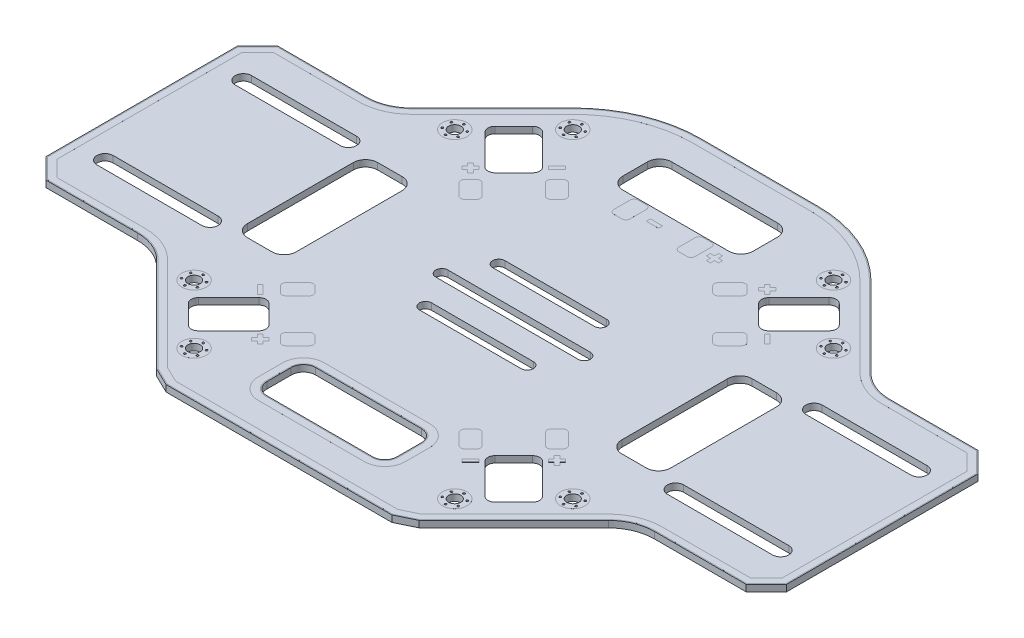
SolidWorks part; units mm, degrees
material "Baseplate Screw Material"
ref_plane "Front Plane" through (0, 0, 0) normal (0, 0, 1) x (1, 0, 0)
ref_plane "Top Plane" through (0, 0, 0) normal (0, 1, 0) x (1, 0, 0)
ref_plane "Right Plane" through (0, 0, 0) normal (1, 0, 0) x (0, 0, -1)
sketch "Sketch1" plane through (0, 0, 0) normal (0, 1, 0) x (1, 0, 0)
  line L0 (0, 60.3186) -> (0, -57.6814) construction
  line L1 (-27.75, -57.6814) -> (27.75, -57.6814)
  line L2 (-13, -47.6814) -> (13, -47.6814)
  line L3 (-16, -38.6814) -> (-16, -44.6814)
  line L4 (16, -38.6814) -> (16, -44.6814)
  line L5 (-16, -41.6814) -> (16, -41.6814) construction
  line L6 (-13, -35.6814) -> (13, -35.6814)
  line L7 (-27.75, -57.6814) -> (-32.25, -55.502)
  line L8 (27.75, -57.6814) -> (32.25, -55.502)
  line L9 (-32.25, -55.502) -> (32.25, -55.502) construction
  line L10 (32.25, -55.502) -> (55.502, -32.25)
  line L11 (-32.25, -55.502) -> (-55.502, -32.25)
  line L12 (-43.876, 43.876) -> (43.876, -43.876) construction
  line L13 (-43.876, -43.876) -> (43.876, 43.876) construction
  line L14 (37.6888, -42.285) -> (42.285, -37.6888)
  line L15 (27.7893, -34.8604) -> (35.2139, -42.285)
  line L16 (34.8604, -27.7893) -> (42.285, -35.2139)
  line L17 (31.5016, -38.5727) -> (38.5727, -31.5016) construction
  line L18 (27.7893, -32.3855) -> (32.3855, -27.7893)
  line L19 (-38.5727, -31.5016) -> (-31.5016, -38.5727) construction
  line L20 (-35.2139, -42.285) -> (-27.7893, -34.8604)
  line L21 (-42.285, -35.2139) -> (-34.8604, -27.7893)
  line L22 (-32.3855, -27.7893) -> (-27.7893, -32.3855)
  line L23 (-42.285, -37.6888) -> (-37.6888, -42.285)
  line L24 (-63.5, -28.9371) -> (63.5, -28.9371) construction
  line L25 (63.5, -28.9371) -> (86, -28.9371)
  line L26 (-63.5, -28.9371) -> (-86, -28.9371)
  line L27 (-91, -23.9371) -> (-91, 23.0629)
  line L28 (91, -23.9371) -> (91, 23.0629)
  line L29 (-86, -28.9371) -> (-86, 28.0629) construction
  line L30 (86, -28.9371) -> (86, 28.0629) construction
  line L31 (-91, -0.4371) -> (-86, -0.4371) construction
  line L32 (86, -0.4371) -> (91, -0.4371) construction
  line L33 (86, -28.9371) -> (91, -23.9371)
  line L34 (-91, -23.9371) -> (-86, -28.9371)
  line L35 (91, 23.0629) -> (86, 28.0629)
  line L36 (-91, 23.0629) -> (-86, 28.0629)
  line L37 (-56.4271, 31.3248) -> (-36.6281, 51.1238)
  line L38 (36.6281, 51.1238) -> (56.4271, 31.3248)
  line L39 (-35.2139, 42.285) -> (-27.7893, 34.8604)
  line L40 (-36.6281, 51.1238) -> (-27.7893, 42.285) construction
  line L41 (-27.7893, 42.285) -> (-31.5016, 38.5727) construction
  line L42 (-42.285, 35.2139) -> (-34.8604, 27.7893)
  line L43 (-31.5016, 38.5727) -> (-38.5727, 31.5016) construction
  line L44 (-42.285, 37.6888) -> (-37.6888, 42.285)
  line L45 (-32.3855, 27.7893) -> (-27.7893, 32.3855)
  line L46 (-86, 28.0629) -> (-64.3021, 28.0629)
  line L47 (86, 28.0629) -> (64.3021, 28.0629)
  line L48 (37.6888, 42.285) -> (42.285, 37.6888)
  line L49 (27.7893, 32.3855) -> (32.3855, 27.7893)
  line L50 (27.7893, 34.8604) -> (35.2139, 42.285)
  line L51 (34.8604, 27.7893) -> (42.285, 35.2139)
  line L52 (31.5016, 38.5727) -> (38.5727, 31.5016) construction
  line L53 (31.5016, 38.5727) -> (27.7893, 42.285) construction
  line L54 (27.7893, 42.285) -> (36.6281, 51.1238) construction
  line L55 (-14.43, 60.3186) -> (14.43, 60.3186)
  line L56 (-13, 51.8186) -> (13, 51.8186)
  line L57 (-13, 39.8186) -> (13, 39.8186)
  line L58 (16, 48.8186) -> (16, 42.8186)
  line L59 (-16, 48.8186) -> (-16, 42.8186)
  line L60 (-12.5, -10.6814) -> (12.5, -10.6814)
  line L61 (-12.5, -7.6814) -> (12.5, -7.6814)
  line L62 (-17.5, -1.6814) -> (17.5, -1.6814)
  line L63 (-17.5, 1.3186) -> (17.5, 1.3186)
  line L64 (-12.5, 7.3186) -> (12.5, 7.3186)
  line L65 (-12.5, 10.3186) -> (12.5, 10.3186)
  line L66 (-52, 12.5629) -> (-52, -13.4371)
  line L67 (-86, -0.4371) -> (-52, -0.4371) construction
  line L68 (-40, 12.5629) -> (-40, -13.4371)
  line L69 (52, 12.5629) -> (52, -13.4371)
  line L70 (-49, 15.5629) -> (-43, 15.5629)
  line L71 (-49, -16.4371) -> (-43, -16.4371)
  line L72 (86, -0.4371) -> (52, -0.4371) construction
  line L73 (40, 12.5629) -> (40, -13.4371)
  line L74 (43, 15.5629) -> (49, 15.5629)
  line L75 (43, -16.4371) -> (49, -16.4371)
  line L76 (-83, 18.5629) -> (-57.2, 18.5629)
  line L77 (-83, 14.5629) -> (-57.2, 14.5629)
  line L78 (-83, -15.4371) -> (-57.2, -15.4371)
  line L79 (-83, -19.4371) -> (-57.2, -19.4371)
  line L80 (57.2, -15.4371) -> (83, -15.4371)
  line L81 (57.2, -19.4371) -> (83, -19.4371)
  line L82 (57.2, 18.5629) -> (83, 18.5629)
  line L83 (57.2, 14.5629) -> (83, 14.5629)
  line L84 (-46.5276, 32.0319) -> (-32.0319, 46.5276) construction
  line L85 (32.0319, -46.5276) -> (46.5276, -32.0319) construction
  arc A0 (-16, -44.6814) -> (-13, -47.6814) centre (-13, -44.6814) ccw
  arc A1 (-13, -35.6814) -> (-16, -38.6814) centre (-13, -38.6814) ccw
  arc A2 (16, -38.6814) -> (13, -35.6814) centre (13, -38.6814) ccw
  arc A3 (13, -47.6814) -> (16, -44.6814) centre (13, -44.6814) ccw
  arc A4 (27.7893, -32.3855) -> (27.7893, -34.8604) centre (29.0267, -33.6229) ccw
  arc A5 (34.8604, -27.7893) -> (32.3855, -27.7893) centre (33.6229, -29.0267) ccw
  arc A6 (35.2139, -42.285) -> (37.6888, -42.285) centre (36.4514, -41.0475) ccw
  arc A7 (42.285, -37.6888) -> (42.285, -35.2139) centre (41.0475, -36.4514) ccw
  arc A8 (-37.6888, -42.285) -> (-35.2139, -42.285) centre (-36.4514, -41.0475) ccw
  arc A9 (-42.285, -35.2139) -> (-42.285, -37.6888) centre (-41.0475, -36.4514) ccw
  arc A10 (-32.3855, -27.7893) -> (-34.8604, -27.7893) centre (-33.6229, -29.0267) ccw
  arc A11 (-27.7893, -34.8604) -> (-27.7893, -32.3855) centre (-29.0267, -33.6229) ccw
  arc A12 (-55.502, -32.25) -> (-63.5, -28.9371) centre (-63.5, -40.248) ccw
  arc A13 (63.5, -28.9371) -> (55.502, -32.25) centre (63.5, -40.248) ccw
  arc A14 (-42.285, 37.6888) -> (-42.285, 35.2139) centre (-41.0475, 36.4514) ccw
  arc A15 (-35.2139, 42.285) -> (-37.6888, 42.285) centre (-36.4514, 41.0475) ccw
  arc A16 (-27.7893, 32.3855) -> (-27.7893, 34.8604) centre (-29.0267, 33.6229) ccw
  arc A17 (-34.8604, 27.7893) -> (-32.3855, 27.7893) centre (-33.6229, 29.0267) ccw
  arc A18 (-64.3021, 28.0629) -> (-56.4271, 31.3248) centre (-64.3021, 39.1998) ccw
  arc A19 (56.4271, 31.3248) -> (64.3021, 28.0629) centre (64.3021, 39.1998) ccw
  arc A20 (27.7893, 34.8604) -> (27.7893, 32.3855) centre (29.0267, 33.6229) ccw
  arc A21 (37.6888, 42.285) -> (35.2139, 42.285) centre (36.4514, 41.0475) ccw
  arc A22 (42.285, 35.2139) -> (42.285, 37.6888) centre (41.0475, 36.4514) ccw
  arc A23 (32.3855, 27.7893) -> (34.8604, 27.7893) centre (33.6229, 29.0267) ccw
  arc A24 (-14.43, 60.3186) -> (-36.6281, 51.1238) centre (-14.43, 28.9257) ccw
  arc A25 (13, 39.8186) -> (16, 42.8186) centre (13, 42.8186) ccw
  arc A26 (36.6281, 51.1238) -> (14.43, 60.3186) centre (14.43, 28.9257) ccw
  arc A27 (16, 48.8186) -> (13, 51.8186) centre (13, 48.8186) ccw
  arc A28 (-16, 42.8186) -> (-13, 39.8186) centre (-13, 42.8186) ccw
  arc A29 (-13, 51.8186) -> (-16, 48.8186) centre (-13, 48.8186) ccw
  arc A30 (-12.5, -7.6814) -> (-12.5, -10.6814) centre (-12.5, -9.1814) ccw
  arc A31 (12.5, -10.6814) -> (12.5, -7.6814) centre (12.5, -9.1814) ccw
  arc A32 (-17.5, 1.3186) -> (-17.5, -1.6814) centre (-17.5, -0.1814) ccw
  arc A33 (17.5, -1.6814) -> (17.5, 1.3186) centre (17.5, -0.1814) ccw
  arc A34 (-12.5, 10.3186) -> (-12.5, 7.3186) centre (-12.5, 8.8186) ccw
  arc A35 (12.5, 7.3186) -> (12.5, 10.3186) centre (12.5, 8.8186) ccw
  arc A36 (-49, 15.5629) -> (-52, 12.5629) centre (-49, 12.5629) ccw
  arc A37 (-40, 12.5629) -> (-43, 15.5629) centre (-43, 12.5629) ccw
  arc A38 (-52, -13.4371) -> (-49, -16.4371) centre (-49, -13.4371) ccw
  arc A39 (-43, -16.4371) -> (-40, -13.4371) centre (-43, -13.4371) ccw
  arc A40 (43, 15.5629) -> (40, 12.5629) centre (43, 12.5629) ccw
  arc A41 (52, 12.5629) -> (49, 15.5629) centre (49, 12.5629) ccw
  arc A42 (40, -13.4371) -> (43, -16.4371) centre (43, -13.4371) ccw
  arc A43 (49, -16.4371) -> (52, -13.4371) centre (49, -13.4371) ccw
  arc A44 (-57.2, 14.5629) -> (-57.2, 18.5629) centre (-57.2, 16.5629) ccw
  arc A45 (-83, 18.5629) -> (-83, 14.5629) centre (-83, 16.5629) ccw
  arc A46 (-83, -15.4371) -> (-83, -19.4371) centre (-83, -17.4371) ccw
  arc A47 (-57.2, -19.4371) -> (-57.2, -15.4371) centre (-57.2, -17.4371) ccw
  arc A48 (57.2, -15.4371) -> (57.2, -19.4371) centre (57.2, -17.4371) ccw
  arc A49 (83, -19.4371) -> (83, -15.4371) centre (83, -17.4371) ccw
  arc A50 (57.2, 18.5629) -> (57.2, 14.5629) centre (57.2, 16.5629) ccw
  arc A51 (83, 14.5629) -> (83, 18.5629) centre (83, 16.5629) ccw
  circle A52 centre (-32.0319, 46.5276) radius 1.5
  circle A53 centre (-46.5276, 32.0319) radius 1.5
  circle A54 centre (32.0319, -46.5276) radius 1.5
  circle A55 centre (46.5276, -32.0319) radius 1.5
  circle A56 centre (-46.5276, -32.0319) radius 1.5
  circle A57 centre (-32.0319, -46.5276) radius 1.5
  circle A58 centre (32.0319, 46.5276) radius 1.5
  circle A59 centre (46.5276, 32.0319) radius 1.5
  point P4 (-35.0371, 35.0371)
  point P5 (0, -47.6814)
  point P14 (0, -41.6814)
  point P15 (0, -35.6814)
  point P19 (0, -55.502)
  point P29 (0, 0)
  point P30 (39.9869, -39.9869)
  point P32 (0, 0)
  point P42 (30.0874, -30.0874)
  point P43 (35.0371, -35.0371)
  point P50 (-35.0371, -35.0371)
  point P53 (-38.5727, -31.5016)
  point P62 (-39.9869, -39.9869)
  point P63 (-30.0874, -30.0874)
  point P70 (0, -28.9371)
  point P99 (-39.9869, 39.9869)
  point P102 (-30.0874, 30.0874)
  point P119 (35.0371, 35.0371)
  point P122 (39.9869, 39.9869)
  point P123 (30.0874, 30.0874)
  point P135 (0, 51.8186)
  point P138 (0, 39.8186)
  point P147 (0, -10.6814)
  point P151 (-14, -9.1814)
  point P153 (14, -9.1814)
  point P156 (0, -1.6814)
  point P158 (-19, -0.1814)
  point P162 (19, -0.1814)
  point P167 (0, 7.3186)
  point P203 (-85, 16.5629)
  point P205 (-55.2, 16.5629)
  point P217 (85, -17.4371)
  point P229 (-39.2798, 39.2798)
  point P232 (39.2798, -39.2798)
  dimension "D5" = 12
  dimension "D6" = 55.5
  dimension "D14" = 14
  dimension "D15" = 127
  dimension "D16" = 22.5
  dimension "D23" = 8.5
  dimension "D24" = 25
  dimension "D25" = 3
  dimension "D28" = 3
  dimension "D31" = 39
  dimension "D32" = 9.5
  dimension "D34" = 29.8
  dimension "D38" = 6
  dimension "D39" = 3
  dimension "D1" = 118
  dimension "D2" = 10
  dimension "D3" = 32
  dimension "D4" = 6
  dimension "D7" = 64.5
  dimension "D8" = 5
  dimension "D9" = 124.1
  dimension "D10" = 45
  dimension "D11" = 5.5
  dimension "D12" = 6.5
  dimension "D13" = 10
  dimension "D17" = 22.5
  dimension "D18" = 5
  dimension "D19" = 45
  dimension "D20" = 47
  dimension "D21" = 28
  dimension "D22" = 5.25
  dimension "D26" = 28
  dimension "D27" = 6
  dimension "D29" = 38
  dimension "D30" = 6
  dimension "D33" = 4
  dimension "D35" = 6
  dimension "D36" = 9.5
  dimension "D37" = 4
  dimension "D40" = 6.5
  dimension "D41" = 6.5
extrude "Boss-Extrude1" add sketch "Sketch1" along normal blind 0.8 and the other way blind 0.8
sketch "Sketch2" plane through (0, 0.8, 0) normal (0, 1, 0) x (1, 0, 0)
  line L0 (-27.6926, -57.4314) -> (27.6926, -57.4314)
  line L1 (-27.75, -57.6814) -> (27.75, -57.6814) construction
  line L2 (-27.6926, -57.4314) -> (-32.1031, -55.2953)
  line L3 (-32.25, -55.502) -> (-27.75, -57.6814) construction
  line L4 (27.6926, -57.4314) -> (32.1031, -55.2953)
  line L5 (27.75, -57.6814) -> (32.25, -55.502) construction
  line L6 (0, -57.6814) -> (0, -57.4314) construction
  line L7 (-32.1031, -55.2953) -> (-55.3252, -32.0732)
  line L8 (-55.502, -32.25) -> (-32.25, -55.502) construction
  line L9 (32.1031, -55.2953) -> (55.3252, -32.0732)
  line L10 (32.25, -55.502) -> (55.502, -32.25) construction
  line L11 (-85.8964, -28.6871) -> (-63.5, -28.6871)
  line L12 (-85.8964, -28.6871) -> (-90.75, -23.8335)
  line L13 (-91, -23.9371) -> (-86, -28.9371) construction
  line L14 (-86, -28.9371) -> (-63.5, -28.9371) construction
  line L15 (63.5, -28.6871) -> (85.8964, -28.6871)
  line L16 (85.8964, -28.6871) -> (90.75, -23.8335)
  line L17 (-90.75, -23.8335) -> (-90.75, 22.9593)
  line L18 (-91, 23.0629) -> (-91, -23.9371) construction
  line L19 (-90.75, 22.9593) -> (-85.8964, 27.8129)
  line L20 (-85.8964, 27.8129) -> (-64.3021, 27.8129)
  line L21 (-64.3021, 28.0629) -> (-86, 28.0629) construction
  line L22 (-56.2503, 31.1481) -> (-36.4514, 50.947)
  line L23 (-36.6281, 51.1238) -> (-56.4271, 31.3248) construction
  line L24 (-14.43, 60.0686) -> (14.43, 60.0686)
  line L25 (14.43, 60.3186) -> (-14.43, 60.3186) construction
  line L26 (56.2503, 31.1481) -> (36.4514, 50.947)
  line L27 (56.4271, 31.3248) -> (36.6281, 51.1238) construction
  line L28 (64.3021, 27.8129) -> (85.8964, 27.8129)
  line L29 (86, 28.0629) -> (64.3021, 28.0629) construction
  line L30 (85.8964, 27.8129) -> (90.75, 22.9593)
  line L31 (91, 23.0629) -> (86, 28.0629) construction
  line L32 (90.75, 22.9593) -> (90.75, -23.8335)
  line L33 (-55.0836, 29.9813) -> (-35.2846, 49.7803)
  line L34 (-14.43, 58.4186) -> (14.43, 58.4186)
  line L35 (55.0836, 29.9813) -> (35.2846, 49.7803)
  line L36 (64.3021, 26.1629) -> (85.213, 26.1629)
  line L37 (85.213, 26.1629) -> (89.1, 22.2759)
  line L38 (89.1, 22.2759) -> (89.1, -23.1501)
  line L39 (85.213, -27.0371) -> (89.1, -23.1501)
  line L40 (63.5, -27.0371) -> (85.213, -27.0371)
  line L41 (31.1332, -53.9317) -> (54.1584, -30.9065)
  line L42 (27.3141, -55.7814) -> (31.1332, -53.9317)
  line L43 (-27.3141, -55.7814) -> (27.3141, -55.7814)
  line L44 (-27.3141, -55.7814) -> (-31.1332, -53.9317)
  line L45 (-31.1332, -53.9317) -> (-54.1584, -30.9065)
  line L46 (-85.213, -27.0371) -> (-63.5, -27.0371)
  line L47 (-85.213, -27.0371) -> (-89.1, -23.1501)
  line L48 (-89.1, -23.1501) -> (-89.1, 22.2759)
  line L49 (-89.1, 22.2759) -> (-85.213, 26.1629)
  line L50 (-85.213, 26.1629) -> (-64.3021, 26.1629)
  line L51 (-13, -35.4314) -> (13, -35.4314)
  line L52 (-16.25, -38.6814) -> (-16.25, -44.6814)
  line L53 (-13, -47.9314) -> (13, -47.9314)
  line L54 (16.25, -44.6814) -> (16.25, -38.6814)
  line L55 (16, -44.6814) -> (16, -38.6814) construction
  line L56 (13, -35.6814) -> (-13, -35.6814) construction
  line L57 (-16, -38.6814) -> (-16, -44.6814) construction
  line L58 (-13, -47.6814) -> (13, -47.6814) construction
  line L59 (-13, -33.6314) -> (13, -33.6314)
  line L60 (18.05, -44.6814) -> (18.05, -38.6814)
  line L61 (-13, -49.7314) -> (13, -49.7314)
  line L62 (-18.05, -38.6814) -> (-18.05, -44.6814)
  line L63 (32.0319, -43.5276) -> (32.0319, -44.2776) construction
  line L64 (-32.0319, -44.2776) -> (-33.9805, -45.4026) construction
  line L65 (-33.9805, -45.4026) -> (-33.9805, -47.6526) construction
  line L66 (-33.9805, -47.6526) -> (-32.0319, -48.7776) construction
  line L67 (-32.0319, -48.7776) -> (-30.0834, -47.6526) construction
  line L68 (-30.0834, -47.6526) -> (-30.0834, -45.4026) construction
  line L69 (-30.0834, -45.4026) -> (-32.0319, -44.2776) construction
  line L70 (-46.5276, -29.7819) -> (-48.4762, -30.9069) construction
  line L71 (-48.4762, -30.9069) -> (-48.4762, -33.1569) construction
  line L72 (-48.4762, -33.1569) -> (-46.5276, -34.2819) construction
  line L73 (-46.5276, -34.2819) -> (-44.5791, -33.1569) construction
  line L74 (-44.5791, -33.1569) -> (-44.5791, -30.9069) construction
  line L75 (-44.5791, -30.9069) -> (-46.5276, -29.7819) construction
  line L76 (-46.5276, 34.2819) -> (-48.4762, 33.1569) construction
  line L77 (-48.4762, 33.1569) -> (-48.4762, 30.9069) construction
  line L78 (-48.4762, 30.9069) -> (-46.5276, 29.7819) construction
  line L79 (-46.5276, 29.7819) -> (-44.5791, 30.9069) construction
  line L80 (-44.5791, 30.9069) -> (-44.5791, 33.1569) construction
  line L81 (-44.5791, 33.1569) -> (-46.5276, 34.2819) construction
  line L82 (-32.0319, 48.7776) -> (-33.9805, 47.6526) construction
  line L83 (-33.9805, 47.6526) -> (-33.9805, 45.4026) construction
  line L84 (-33.9805, 45.4026) -> (-32.0319, 44.2776) construction
  line L85 (-32.0319, 44.2776) -> (-30.0834, 45.4026) construction
  line L86 (-30.0834, 45.4026) -> (-30.0834, 47.6526) construction
  line L87 (-30.0834, 47.6526) -> (-32.0319, 48.7776) construction
  line L88 (32.0319, 48.7776) -> (30.0834, 47.6526) construction
  line L89 (30.0834, 47.6526) -> (30.0834, 45.4026) construction
  line L90 (30.0834, 45.4026) -> (32.0319, 44.2776) construction
  line L91 (32.0319, 44.2776) -> (33.9805, 45.4026) construction
  line L92 (33.9805, 45.4026) -> (33.9805, 47.6526) construction
  line L93 (33.9805, 47.6526) -> (32.0319, 48.7776) construction
  line L94 (46.5276, 34.2819) -> (44.5791, 33.1569) construction
  line L95 (44.5791, 33.1569) -> (44.5791, 30.9069) construction
  line L96 (44.5791, 30.9069) -> (46.5276, 29.7819) construction
  line L97 (46.5276, 29.7819) -> (48.4762, 30.9069) construction
  line L98 (48.4762, 30.9069) -> (48.4762, 33.1569) construction
  line L99 (48.4762, 33.1569) -> (46.5276, 34.2819) construction
  line L100 (46.5276, -29.7819) -> (44.5791, -30.9069) construction
  line L101 (44.5791, -30.9069) -> (44.5791, -33.1569) construction
  line L102 (44.5791, -33.1569) -> (46.5276, -34.2819) construction
  line L103 (46.5276, -34.2819) -> (48.4762, -33.1569) construction
  line L104 (48.4762, -33.1569) -> (48.4762, -30.9069) construction
  line L105 (48.4762, -30.9069) -> (46.5276, -29.7819) construction
  line L106 (32.0319, -44.2776) -> (30.0834, -45.4026) construction
  line L107 (30.0834, -45.4026) -> (30.0834, -47.6526) construction
  line L108 (30.0834, -47.6526) -> (32.0319, -48.7776) construction
  line L109 (32.0319, -48.7776) -> (33.9805, -47.6526) construction
  line L110 (33.9805, -47.6526) -> (33.9805, -45.4026) construction
  line L111 (33.9805, -45.4026) -> (32.0319, -44.2776) construction
  line L112 (32.0319, -44.2776) -> (32.0319, -45.0276) construction
  arc A0 (-55.3252, -32.0732) -> (-63.5, -28.6871) centre (-63.5, -40.248) ccw
  arc A1 (-55.502, -32.25) -> (-63.5, -28.9371) centre (-63.5, -40.248) ccw construction
  arc A2 (63.5, -28.6871) -> (55.3252, -32.0732) centre (63.5, -40.248) ccw
  arc A3 (63.5, -28.9371) -> (55.502, -32.25) centre (63.5, -40.248) ccw construction
  arc A4 (-64.3021, 27.8129) -> (-56.2503, 31.1481) centre (-64.3021, 39.1998) ccw
  arc A5 (-64.3021, 28.0629) -> (-56.4271, 31.3248) centre (-64.3021, 39.1998) ccw construction
  arc A6 (-14.43, 60.0686) -> (-36.4514, 50.947) centre (-14.43, 28.9257) ccw
  arc A7 (-14.43, 60.3186) -> (-36.6281, 51.1238) centre (-14.43, 28.9257) ccw construction
  arc A8 (36.4514, 50.947) -> (14.43, 60.0686) centre (14.43, 28.9257) ccw
  arc A9 (36.6281, 51.1238) -> (14.43, 60.3186) centre (14.43, 28.9257) ccw construction
  arc A10 (56.2503, 31.1481) -> (64.3021, 27.8129) centre (64.3021, 39.1998) ccw
  arc A11 (56.4271, 31.3248) -> (64.3021, 28.0629) centre (64.3021, 39.1998) ccw construction
  arc A12 (-14.43, 58.4186) -> (-35.2846, 49.7803) centre (-14.43, 28.9257) ccw
  arc A13 (35.2846, 49.7803) -> (14.43, 58.4186) centre (14.43, 28.9257) ccw
  arc A14 (55.0836, 29.9813) -> (64.3021, 26.1629) centre (64.3021, 39.1998) ccw
  arc A15 (63.5, -27.0371) -> (54.1584, -30.9065) centre (63.5, -40.248) ccw
  arc A16 (-54.1584, -30.9065) -> (-63.5, -27.0371) centre (-63.5, -40.248) ccw
  arc A17 (-64.3021, 26.1629) -> (-55.0836, 29.9813) centre (-64.3021, 39.1998) ccw
  arc A18 (-13, -35.4314) -> (-16.25, -38.6814) centre (-13, -38.6814) ccw
  arc A19 (16.25, -38.6814) -> (13, -35.4314) centre (13, -38.6814) ccw
  arc A20 (-16.25, -44.6814) -> (-13, -47.9314) centre (-13, -44.6814) ccw
  arc A21 (13, -47.9314) -> (16.25, -44.6814) centre (13, -44.6814) ccw
  arc A22 (-13, -35.6814) -> (-16, -38.6814) centre (-13, -38.6814) ccw construction
  arc A23 (-16, -44.6814) -> (-13, -47.6814) centre (-13, -44.6814) ccw construction
  arc A24 (16, -38.6814) -> (13, -35.6814) centre (13, -38.6814) ccw construction
  arc A25 (13, -47.6814) -> (16, -44.6814) centre (13, -44.6814) ccw construction
  arc A26 (18.05, -38.6814) -> (13, -33.6314) centre (13, -38.6814) ccw
  arc A27 (13, -49.7314) -> (18.05, -44.6814) centre (13, -44.6814) ccw
  arc A28 (-18.05, -44.6814) -> (-13, -49.7314) centre (-13, -44.6814) ccw
  arc A29 (-13, -33.6314) -> (-18.05, -38.6814) centre (-13, -38.6814) ccw
  circle A30 centre (-32.0319, -46.5276) radius 1.5
  circle A31 centre (-46.5276, -32.0319) radius 1.5
  circle A32 centre (-46.5276, 32.0319) radius 1.5
  circle A33 centre (-32.0319, 46.5276) radius 1.5
  circle A34 centre (32.0319, 46.5276) radius 1.5
  circle A35 centre (46.5276, 32.0319) radius 1.5
  circle A36 centre (46.5276, -32.0319) radius 1.5
  circle A37 centre (32.0319, -46.5276) radius 1.5
  circle A38 centre (-32.0319, -46.5276) radius 1.5 construction
  circle A39 centre (-46.5276, -32.0319) radius 1.5 construction
  circle A40 centre (-46.5276, 32.0319) radius 1.5 construction
  circle A41 centre (-32.0319, 46.5276) radius 1.5 construction
  circle A42 centre (32.0319, 46.5276) radius 1.5 construction
  circle A43 centre (46.5276, 32.0319) radius 1.5 construction
  circle A44 centre (46.5276, -32.0319) radius 1.5 construction
  circle A45 centre (32.0319, -46.5276) radius 1.5 construction
  circle A46 centre (-32.0319, -46.5276) radius 3
  circle A47 centre (-46.5276, -32.0319) radius 3
  circle A48 centre (-46.5276, 32.0319) radius 3
  circle A49 centre (-32.0319, 46.5276) radius 3
  circle A50 centre (32.0319, 46.5276) radius 3
  circle A51 centre (46.5276, 32.0319) radius 3
  circle A52 centre (46.5276, -32.0319) radius 3
  circle A53 centre (32.0319, -46.5276) radius 3
  circle A54 centre (-32.0319, -46.5276) radius 1.9486 construction
  circle A55 centre (-46.5276, -32.0319) radius 1.9486 construction
  circle A56 centre (-46.5276, 32.0319) radius 1.9486 construction
  circle A57 centre (-32.0319, 46.5276) radius 1.9486 construction
  circle A58 centre (32.0319, 46.5276) radius 1.9486 construction
  circle A59 centre (46.5276, 32.0319) radius 1.9486 construction
  circle A60 centre (46.5276, -32.0319) radius 1.9486 construction
  circle A61 centre (32.0319, -46.5276) radius 1.9486 construction
  circle A62 centre (32.0319, -44.2776) radius 0.25
  circle A63 centre (33.9805, -45.4026) radius 0.25
  circle A64 centre (33.9805, -47.6526) radius 0.25
  circle A65 centre (32.0319, -48.7776) radius 0.25
  circle A66 centre (30.0834, -47.6526) radius 0.25
  circle A67 centre (30.0834, -45.4026) radius 0.25
  circle A68 centre (46.5276, -34.2819) radius 0.25
  circle A69 centre (48.4762, -33.1569) radius 0.25
  circle A70 centre (48.4762, -30.9069) radius 0.25
  circle A71 centre (46.5276, -29.7819) radius 0.25
  circle A72 centre (44.5791, -30.9069) radius 0.25
  circle A73 centre (44.5791, -33.1569) radius 0.25
  circle A74 centre (46.5276, 29.7819) radius 0.25
  circle A75 centre (48.4762, 30.9069) radius 0.25
  circle A76 centre (48.4762, 33.1569) radius 0.25
  circle A77 centre (46.5276, 34.2819) radius 0.25
  circle A78 centre (44.5791, 33.1569) radius 0.25
  circle A79 centre (44.5791, 30.9069) radius 0.25
  circle A80 centre (32.0319, 44.2776) radius 0.25
  circle A81 centre (33.9805, 45.4026) radius 0.25
  circle A82 centre (33.9805, 47.6526) radius 0.25
  circle A83 centre (32.0319, 48.7776) radius 0.25
  circle A84 centre (30.0834, 47.6526) radius 0.25
  circle A85 centre (30.0834, 45.4026) radius 0.25
  circle A86 centre (-32.0319, 48.7776) radius 0.25
  circle A87 centre (-30.0834, 47.6526) radius 0.25
  circle A88 centre (-30.0834, 45.4026) radius 0.25
  circle A89 centre (-32.0319, 44.2776) radius 0.25
  circle A90 centre (-33.9805, 47.6526) radius 0.25
  circle A91 centre (-33.9805, 45.4026) radius 0.25
  circle A92 centre (-46.5276, 29.7819) radius 0.25
  circle A93 centre (-44.5791, 30.9069) radius 0.25
  circle A94 centre (-44.5791, 33.1569) radius 0.25
  circle A95 centre (-46.5276, 34.2819) radius 0.25
  circle A96 centre (-48.4762, 33.1569) radius 0.25
  circle A97 centre (-48.4762, 30.9069) radius 0.25
  circle A98 centre (-46.5276, -29.7819) radius 0.25
  circle A99 centre (-44.5791, -30.9069) radius 0.25
  circle A100 centre (-44.5791, -33.1569) radius 0.25
  circle A101 centre (-46.5276, -34.2819) radius 0.25
  circle A102 centre (-48.4762, -33.1569) radius 0.25
  circle A103 centre (-48.4762, -30.9069) radius 0.25
  circle A104 centre (-32.0319, -44.2776) radius 0.25
  circle A105 centre (-30.0834, -45.4026) radius 0.25
  circle A106 centre (-30.0834, -47.6526) radius 0.25
  circle A107 centre (-32.0319, -48.7776) radius 0.25
  circle A108 centre (-33.9805, -47.6526) radius 0.25
  circle A109 centre (-33.9805, -45.4026) radius 0.25
  dimension "D2" = 0.25
  dimension "D5" = 0.25
  dimension "D7" = 1.65
  dimension "D8" = 0.25
  dimension "D10" = 6
  dimension "D11" = 0.5
  dimension "D1" = 0.25
  dimension "D3" = 0.25
  dimension "D4" = 0.25
  dimension "D6" = 0.25
  dimension "D9" = 1.8
extrude "Boss-Extrude2" add sketch "Sketch2" along normal blind 0.001 contours A10 L26 A8 L24 A6 L22 A4 L20 L19 L17 L12 L11 A0 L7 L2 L0 L4 L9 A2 L15 L16 L32 L30 L28 L50 A17 L33 A12 L34 A13 L35 A14 L36 L37 L38 L39 L40 A15 L41 L42 L43 L44 L45 A16 L46 L47 L48 L49 | A46 A109 A108 A107 A106 A105 A104 A30 | A47 A103 A102 A101 A100 A99 A98 A31 | A48 A97 A96 A95 A94 A93 A92 A32 | A49 A91 A90 A89 A88 A87 A86 A33 | A50 A85 A84 A83 A82 A81 A80 A34 | A51 A79 A78 A77 A76 A75 A74 A35 | A52 A73 A72 A71 A70 A69 A68 A36 | A53 A67 A66 A65 A64 A63 A62 A37 | L59 A29 L62 A28 L61 A27 L60 A26 A21 L53 A20 L52 A18 L51 A19 L54 region at (-29.8036, 0.8, 56.1688) region at (0, 0.8, 34.0267) region at (-34.9471, 0.8, 46.5276) region at (-49.4428, 0.8, 32.0319) region at (-49.4428, 0.8, -32.0319) region at (-34.9471, 0.8, -46.5276) region at (29.1168, 0.8, -46.5276) region at (43.6125, 0.8, -32.0319) region at (43.6125, 0.8, 32.0319) region at (29.1168, 0.8, 46.5276)
mirror "Mirror1" about plane through (0, 0, 0) normal (0, 1, 0) of "Boss-Extrude2"
sketch "Sketch3" plane through (0, -0.8, 0) normal (0, -1, 0) x (1, 0, 0)
  line L0 (0, 49.7314) -> (0, 51.7314) construction
  line L1 (-13, 49.7314) -> (13, 49.7314) construction
  line L2 (-27.3141, 55.7814) -> (27.3141, 55.7814) construction
  line L3 (11, 51.7314) -> (-11, 51.7314) construction
  line L4 (11, 53.7814) -> (-11, 53.7814) construction
  line L5 (0, 53.7814) -> (0, 55.7814) construction
  line L6 (11, 51.7314) -> (11, 53.7814) construction
  line L7 (-11, 51.7314) -> (-11, 53.7814) construction
  line L8 (11.29, 53.7814) -> (-10.71, 53.7814) construction
  text T0 "<b>DJI INNOVATIONS</b>" font "MS Reference Sans Serif" height 2.05
  point P8 (0, 51.7314)
  point P11 (0, 53.7814)
  dimension "D1" = 2
  dimension "D2" = 22
  dimension "D3" = 0.29
extrude "Boss-Extrude3" add sketch "Sketch3" along normal blind 0.001
sketch "Sketch4" plane through (0, -0.8, 0) normal (0, -1, 0) x (1, 0, 0)
  line L0 (9.1282, 51.7314) -> (9.1282, 51.9909)
  line L1 (9.1282, 51.9909) -> (8.7389, 51.9909)
  line L2 (8.7389, 51.9909) -> (8.7389, 51.7314)
  line L3 (9.1282, 51.7314) -> (8.4275, 51.7314) construction
  line L4 (8.7389, 51.7314) -> (9.1282, 51.7314)
  line L6 (-3.2442, 51.7314) -> (-3.2442, 52.0168)
  line L7 (-3.2442, 52.0168) -> (-3.3442, 52.0168)
  line L8 (-3.893, 52.0168) -> (-3.2442, 52.0168) construction
  line L9 (-3.3442, 52.0168) -> (-3.3442, 51.7314)
  line L10 (-3.2442, 51.7314) -> (-4.8531, 51.7314) construction
  line L11 (-3.3442, 51.7314) -> (-3.2442, 51.7314)
  line L12 (-4.8531, 51.7314) -> (-4.7531, 51.7314)
  line L13 (-4.7531, 51.7314) -> (-4.7531, 52.0168)
  line L14 (-4.8531, 52.0168) -> (-4.2044, 52.0168) construction
  line L15 (-4.7531, 52.0168) -> (-4.8531, 52.0168)
  line L16 (-4.8531, 52.0168) -> (-4.8531, 51.7314)
  dimension "D1" = 0.1
extrude "Cut-Extrude1" cut sketch "Sketch4" along normal up to surface (0.001 mm away) up to face at (8.9409, -0.801, 52.931)
sketch "Sketch5" plane through (0, 0.8, 0) normal (0, 1, 0) x (1, 0, 0)
  line L0 (35.7442, -27.259) -> (36.4514, -26.5519)
  line L1 (35.0371, -26.5519) -> (35.7442, -25.8448)
  line L2 (35.3907, -26.9054) -> (37.512, -24.7841) construction
  line L3 (35.0371, -26.5519) -> (35.7442, -27.259)
  line L4 (37.1585, -24.4305) -> (37.8656, -25.1376)
  line L5 (42.285, -35.2139) -> (34.8604, -27.7893) construction
  line L6 (32.1031, -55.2953) -> (55.3252, -32.0732) construction
  line L8 (35.3907, -24.7841) -> (37.512, -26.9054) construction
  line L9 (35.0371, -25.1376) -> (35.7442, -24.4305)
  line L10 (37.1585, -27.259) -> (37.8656, -26.5519)
  line L11 (35.0371, -25.1376) -> (35.7442, -25.8448)
  line L12 (35.7442, -24.4305) -> (36.4514, -25.1376)
  line L13 (36.4514, -26.5519) -> (37.1585, -27.259)
  line L14 (36.4514, -25.1376) -> (37.1585, -24.4305)
  line L15 (37.1585, -25.8448) -> (37.8656, -26.5519)
  line L16 (37.1585, -25.8448) -> (37.8656, -25.1376)
  line L17 (26.9054, -35.3907) -> (24.7841, -37.512) construction
  line L18 (26.5519, -35.0371) -> (27.259, -35.7442)
  line L19 (27.7893, -34.8604) -> (35.2139, -42.285) construction
  line L20 (24.4305, -37.1585) -> (25.1376, -37.8656)
  line L21 (24.4305, -37.1585) -> (26.5519, -35.0371)
  line L22 (25.1376, -37.8656) -> (27.259, -35.7442)
  line L23 (-37.1585, -24.4305) -> (-37.8656, -25.1376)
  line L24 (-37.1585, -24.4305) -> (-35.0371, -26.5519)
  line L25 (-37.8656, -25.1376) -> (-35.7442, -27.259)
  line L26 (-35.3907, -26.9054) -> (-37.512, -24.7841) construction
  line L27 (-35.0371, -26.5519) -> (-35.7442, -27.259)
  line L28 (-26.5519, -35.0371) -> (-27.259, -35.7442)
  line L29 (-27.259, -35.7442) -> (-26.5519, -36.4514)
  line L30 (-26.5519, -36.4514) -> (-27.259, -37.1585)
  line L31 (-27.259, -37.1585) -> (-26.5519, -37.8656)
  line L32 (-25.8448, -37.1585) -> (-26.5519, -37.8656)
  line L33 (-25.8448, -37.1585) -> (-25.1376, -37.8656)
  line L34 (-24.4305, -37.1585) -> (-25.1376, -37.8656)
  line L35 (-25.1376, -36.4514) -> (-24.4305, -37.1585)
  line L36 (-24.4305, -35.7442) -> (-25.1376, -36.4514)
  line L37 (-25.1376, -35.0371) -> (-24.4305, -35.7442)
  line L38 (-25.1376, -35.0371) -> (-25.8448, -35.7442)
  line L39 (-26.5519, -35.0371) -> (-25.8448, -35.7442)
  line L40 (-26.9054, -35.3907) -> (-24.7841, -37.512) construction
  line L41 (-24.7841, -35.3907) -> (-26.9054, -37.512) construction
  line L42 (-24.4305, 37.1585) -> (-25.1376, 37.8656)
  line L43 (-24.4305, 37.1585) -> (-26.5519, 35.0371)
  line L44 (-25.1376, 37.8656) -> (-27.259, 35.7442)
  line L45 (-26.9054, 35.3907) -> (-24.7841, 37.512) construction
  line L46 (-26.5519, 35.0371) -> (-27.259, 35.7442)
  line L47 (-35.0371, 26.5519) -> (-35.7442, 27.259)
  line L48 (-35.7442, 27.259) -> (-36.4514, 26.5519)
  line L49 (-36.4514, 26.5519) -> (-37.1585, 27.259)
  line L50 (-37.1585, 27.259) -> (-37.8656, 26.5519)
  line L51 (-37.1585, 25.8448) -> (-37.8656, 26.5519)
  line L52 (-37.1585, 25.8448) -> (-37.8656, 25.1376)
  line L53 (-37.1585, 24.4305) -> (-37.8656, 25.1376)
  line L54 (-36.4514, 25.1376) -> (-37.1585, 24.4305)
  line L55 (-35.7442, 24.4305) -> (-36.4514, 25.1376)
  line L56 (-35.0371, 25.1376) -> (-35.7442, 24.4305)
  line L57 (-35.0371, 25.1376) -> (-35.7442, 25.8448)
  line L58 (-35.0371, 26.5519) -> (-35.7442, 25.8448)
  line L59 (-35.3907, 26.9054) -> (-37.512, 24.7841) construction
  line L60 (-35.3907, 24.7841) -> (-37.512, 26.9054) construction
  line L61 (37.1585, 24.4305) -> (37.8656, 25.1376)
  line L62 (37.1585, 24.4305) -> (35.0371, 26.5519)
  line L63 (37.8656, 25.1376) -> (35.7442, 27.259)
  line L64 (35.3907, 26.9054) -> (37.512, 24.7841) construction
  line L65 (35.0371, 26.5519) -> (35.7442, 27.259)
  line L66 (26.5519, 35.0371) -> (27.259, 35.7442)
  line L67 (27.259, 35.7442) -> (26.5519, 36.4514)
  line L68 (26.5519, 36.4514) -> (27.259, 37.1585)
  line L69 (27.259, 37.1585) -> (26.5519, 37.8656)
  line L70 (25.8448, 37.1585) -> (26.5519, 37.8656)
  line L71 (25.8448, 37.1585) -> (25.1376, 37.8656)
  line L72 (24.4305, 37.1585) -> (25.1376, 37.8656)
  line L73 (25.1376, 36.4514) -> (24.4305, 37.1585)
  line L74 (24.4305, 35.7442) -> (25.1376, 36.4514)
  line L75 (25.1376, 35.0371) -> (24.4305, 35.7442)
  line L76 (25.1376, 35.0371) -> (25.8448, 35.7442)
  line L77 (26.5519, 35.0371) -> (25.8448, 35.7442)
  line L78 (26.9054, 35.3907) -> (24.7841, 37.512) construction
  line L79 (24.7841, 35.3907) -> (26.9054, 37.512) construction
  line L80 (-36.6281, 51.1238) -> (-56.4271, 31.3248) construction
  line L81 (29.0267, -19.8343) -> (30.4409, -18.4201)
  line L82 (31.8552, -18.4201) -> (34.6836, -21.2486)
  line L83 (29.0267, -21.2486) -> (31.8552, -24.077)
  line L84 (33.2694, -24.077) -> (34.6836, -22.6628)
  line L85 (30.4409, -22.6628) -> (33.2694, -19.8343) construction
  line L86 (29.7338, -19.1272) -> (33.9765, -23.3699) construction
  line L87 (32.3855, -27.7893) -> (27.7893, -32.3855) construction
  line L88 (18.4201, -31.8552) -> (21.2486, -34.6836)
  line L89 (18.4201, -30.4409) -> (19.8343, -29.0267)
  line L90 (21.2486, -29.0267) -> (24.077, -31.8552)
  line L91 (22.6628, -34.6836) -> (24.077, -33.2694)
  line L92 (19.8343, -33.2694) -> (22.6628, -30.4409) construction
  line L93 (19.1272, -29.7338) -> (23.3699, -33.9765) construction
  line L94 (-34.6836, -22.6628) -> (-33.2694, -24.077)
  line L95 (-31.8552, -18.4201) -> (-34.6836, -21.2486)
  line L96 (-30.4409, -18.4201) -> (-29.0267, -19.8343)
  line L97 (-29.0267, -21.2486) -> (-31.8552, -24.077)
  line L98 (-29.7338, -19.1272) -> (-33.9765, -23.3699) construction
  line L99 (-33.2694, -19.8343) -> (-30.4409, -22.6628) construction
  line L100 (-21.2486, -29.0267) -> (-24.077, -31.8552)
  line L101 (-24.077, -33.2694) -> (-22.6628, -34.6836)
  line L102 (-18.4201, -31.8552) -> (-21.2486, -34.6836)
  line L103 (-19.8343, -29.0267) -> (-18.4201, -30.4409)
  line L104 (-19.1272, -29.7338) -> (-23.3699, -33.9765) construction
  line L105 (-22.6628, -30.4409) -> (-19.8343, -33.2694) construction
  line L106 (-22.6628, 34.6836) -> (-24.077, 33.2694)
  line L107 (-18.4201, 31.8552) -> (-21.2486, 34.6836)
  line L108 (-18.4201, 30.4409) -> (-19.8343, 29.0267)
  line L109 (-21.2486, 29.0267) -> (-24.077, 31.8552)
  line L110 (-19.1272, 29.7338) -> (-23.3699, 33.9765) construction
  line L111 (-19.8343, 33.2694) -> (-22.6628, 30.4409) construction
  line L112 (-29.0267, 21.2486) -> (-31.8552, 24.077)
  line L113 (-33.2694, 24.077) -> (-34.6836, 22.6628)
  line L114 (-31.8552, 18.4201) -> (-34.6836, 21.2486)
  line L115 (-29.0267, 19.8343) -> (-30.4409, 18.4201)
  line L116 (-29.7338, 19.1272) -> (-33.9765, 23.3699) construction
  line L117 (-30.4409, 22.6628) -> (-33.2694, 19.8343) construction
  line L118 (34.6836, 22.6628) -> (33.2694, 24.077)
  line L119 (31.8552, 18.4201) -> (34.6836, 21.2486)
  line L120 (30.4409, 18.4201) -> (29.0267, 19.8343)
  line L121 (29.0267, 21.2486) -> (31.8552, 24.077)
  line L122 (29.7338, 19.1272) -> (33.9765, 23.3699) construction
  line L123 (33.2694, 19.8343) -> (30.4409, 22.6628) construction
  line L124 (21.2486, 29.0267) -> (24.077, 31.8552)
  line L125 (24.077, 33.2694) -> (22.6628, 34.6836)
  line L126 (18.4201, 31.8552) -> (21.2486, 34.6836)
  line L127 (19.8343, 29.0267) -> (18.4201, 30.4409)
  line L128 (19.1272, 29.7338) -> (23.3699, 33.9765) construction
  line L129 (22.6628, 30.4409) -> (19.8343, 33.2694) construction
  line L130 (32.25, -55.502) -> (55.502, -32.25) construction
  arc A0 (31.8552, -18.4201) -> (30.4409, -18.4201) centre (31.1481, -19.1272) ccw
  arc A1 (29.0267, -19.8343) -> (29.0267, -21.2486) centre (29.7338, -20.5415) ccw
  arc A2 (31.8552, -24.077) -> (33.2694, -24.077) centre (32.5623, -23.3699) ccw
  arc A3 (34.6836, -22.6628) -> (34.6836, -21.2486) centre (33.9765, -21.9557) ccw
  arc A4 (18.4201, -30.4409) -> (18.4201, -31.8552) centre (19.1272, -31.1481) ccw
  arc A5 (21.2486, -29.0267) -> (19.8343, -29.0267) centre (20.5415, -29.7338) ccw
  arc A6 (24.077, -33.2694) -> (24.077, -31.8552) centre (23.3699, -32.5623) ccw
  arc A7 (21.2486, -34.6836) -> (22.6628, -34.6836) centre (21.9557, -33.9765) ccw
  arc A8 (-33.2694, -24.077) -> (-31.8552, -24.077) centre (-32.5623, -23.3699) ccw
  arc A9 (-34.6836, -21.2486) -> (-34.6836, -22.6628) centre (-33.9765, -21.9557) ccw
  arc A10 (-30.4409, -18.4201) -> (-31.8552, -18.4201) centre (-31.1481, -19.1272) ccw
  arc A11 (-29.0267, -21.2486) -> (-29.0267, -19.8343) centre (-29.7338, -20.5415) ccw
  arc A12 (-24.077, -31.8552) -> (-24.077, -33.2694) centre (-23.3699, -32.5623) ccw
  arc A13 (-22.6628, -34.6836) -> (-21.2486, -34.6836) centre (-21.9557, -33.9765) ccw
  arc A14 (-18.4201, -31.8552) -> (-18.4201, -30.4409) centre (-19.1272, -31.1481) ccw
  arc A15 (-19.8343, -29.0267) -> (-21.2486, -29.0267) centre (-20.5415, -29.7338) ccw
  arc A16 (-24.077, 33.2694) -> (-24.077, 31.8552) centre (-23.3699, 32.5623) ccw
  arc A17 (-21.2486, 34.6836) -> (-22.6628, 34.6836) centre (-21.9557, 33.9765) ccw
  arc A18 (-18.4201, 30.4409) -> (-18.4201, 31.8552) centre (-19.1272, 31.1481) ccw
  arc A19 (-21.2486, 29.0267) -> (-19.8343, 29.0267) centre (-20.5415, 29.7338) ccw
  arc A20 (-31.8552, 24.077) -> (-33.2694, 24.077) centre (-32.5623, 23.3699) ccw
  arc A21 (-34.6836, 22.6628) -> (-34.6836, 21.2486) centre (-33.9765, 21.9557) ccw
  arc A22 (-31.8552, 18.4201) -> (-30.4409, 18.4201) centre (-31.1481, 19.1272) ccw
  arc A23 (-29.0267, 19.8343) -> (-29.0267, 21.2486) centre (-29.7338, 20.5415) ccw
  arc A24 (33.2694, 24.077) -> (31.8552, 24.077) centre (32.5623, 23.3699) ccw
  arc A25 (34.6836, 21.2486) -> (34.6836, 22.6628) centre (33.9765, 21.9557) ccw
  arc A26 (30.4409, 18.4201) -> (31.8552, 18.4201) centre (31.1481, 19.1272) ccw
  arc A27 (29.0267, 21.2486) -> (29.0267, 19.8343) centre (29.7338, 20.5415) ccw
  arc A28 (24.077, 31.8552) -> (24.077, 33.2694) centre (23.3699, 32.5623) ccw
  arc A29 (22.6628, 34.6836) -> (21.2486, 34.6836) centre (21.9557, 33.9765) ccw
  arc A30 (18.4201, 31.8552) -> (18.4201, 30.4409) centre (19.1272, 31.1481) ccw
  arc A31 (19.8343, 29.0267) -> (21.2486, 29.0267) centre (20.5415, 29.7338) ccw
  point P14 (36.4514, -25.8448)
  point P17 (35.3907, -24.7841)
  point P101 (0, 0)
  point P111 (31.8552, -21.2486)
  point P234 (0, 0)
  dimension "D8" = 2
  dimension "D1" = 3
  dimension "D2" = 1
  dimension "D3" = 18
  dimension "D4" = 1
  dimension "D5" = 1
  dimension "D6" = 4
  dimension "D7" = 18
  dimension "D9" = 4
  dimension "D10" = 2
  dimension "D11" = 4
  dimension "D13" = 4
  dimension "D12" = 15
  dimension "D14" = 2
extrude "Boss-Extrude4" add sketch "Sketch5" along normal blind 0.001
sketch "Sketch6" plane through (0, 0.8, 0) normal (0, 1, 0) x (1, 0, 0)
  circle A0 centre (-48.4762, 33.1569) radius 0.25
  circle A1 centre (-46.5276, 34.2819) radius 0.25
  circle A2 centre (-44.5791, 33.1569) radius 0.25
  circle A3 centre (-48.4762, 30.9069) radius 0.25
  circle A4 centre (-46.5276, 29.7819) radius 0.25
  circle A5 centre (-44.5791, 30.9069) radius 0.25
  circle A6 centre (-33.9805, 45.4026) radius 0.25
  circle A7 centre (-32.0319, 48.7776) radius 0.25
  circle A8 centre (-33.9805, 47.6526) radius 0.25
  circle A9 centre (-32.0319, 44.2776) radius 0.25
  circle A10 centre (-30.0834, 47.6526) radius 0.25
  circle A11 centre (-30.0834, 45.4026) radius 0.25
  circle A12 centre (30.0834, 47.6526) radius 0.25
  circle A13 centre (32.0319, 48.7776) radius 0.25
  circle A14 centre (33.9805, 47.6526) radius 0.25
  circle A15 centre (33.9805, 45.4026) radius 0.25
  circle A16 centre (30.0834, 45.4026) radius 0.25
  circle A17 centre (32.0319, 44.2776) radius 0.25
  circle A18 centre (46.5276, 34.2819) radius 0.25
  circle A19 centre (48.4762, 30.9069) radius 0.25
  circle A20 centre (44.5791, 33.1569) radius 0.25
  circle A21 centre (48.4762, 33.1569) radius 0.25
  circle A22 centre (46.5276, 29.7819) radius 0.25
  circle A23 centre (44.5791, 30.9069) radius 0.25
  circle A24 centre (44.5791, -30.9069) radius 0.25
  circle A25 centre (46.5276, -29.7819) radius 0.25
  circle A26 centre (44.5791, -33.1569) radius 0.25
  circle A27 centre (48.4762, -33.1569) radius 0.25
  circle A28 centre (48.4762, -30.9069) radius 0.25
  circle A29 centre (46.5276, -34.2819) radius 0.25
  circle A30 centre (32.0319, -44.2776) radius 0.25
  circle A31 centre (30.0834, -45.4026) radius 0.25
  circle A32 centre (30.0834, -47.6526) radius 0.25
  circle A33 centre (33.9805, -47.6526) radius 0.25
  circle A34 centre (32.0319, -48.7776) radius 0.25
  circle A35 centre (33.9805, -45.4026) radius 0.25
  circle A36 centre (-48.4762, -30.9069) radius 0.25
  circle A37 centre (-44.5791, -30.9069) radius 0.25
  circle A38 centre (-48.4762, -33.1569) radius 0.25
  circle A39 centre (-46.5276, -34.2819) radius 0.25
  circle A40 centre (-44.5791, -33.1569) radius 0.25
  circle A41 centre (-46.5276, -29.7819) radius 0.25
  circle A42 centre (-33.9805, -45.4026) radius 0.25
  circle A43 centre (-32.0319, -44.2776) radius 0.25
  circle A44 centre (-30.0834, -45.4026) radius 0.25
  circle A45 centre (-30.0834, -47.6526) radius 0.25
  circle A46 centre (-33.9805, -47.6526) radius 0.25
  circle A47 centre (-32.0319, -48.7776) radius 0.25
  circle A48 centre (-48.4762, 33.1569) radius 0.25 construction
  circle A49 centre (-46.5276, 34.2819) radius 0.25 construction
  circle A50 centre (-44.5791, 33.1569) radius 0.25 construction
  circle A51 centre (-44.5791, 30.9069) radius 0.25 construction
  circle A52 centre (-46.5276, 29.7819) radius 0.25 construction
  circle A53 centre (-48.4762, 30.9069) radius 0.25 construction
  circle A54 centre (-33.9805, 45.4026) radius 0.25 construction
  circle A55 centre (-33.9805, 47.6526) radius 0.25 construction
  circle A56 centre (-32.0319, 48.7776) radius 0.25 construction
  circle A57 centre (-30.0834, 47.6526) radius 0.25 construction
  circle A58 centre (-30.0834, 45.4026) radius 0.25 construction
  circle A59 centre (-32.0319, 44.2776) radius 0.25 construction
  circle A60 centre (32.0319, 44.2776) radius 0.25 construction
  circle A61 centre (30.0834, 45.4026) radius 0.25 construction
  circle A62 centre (30.0834, 47.6526) radius 0.25 construction
  circle A63 centre (32.0319, 48.7776) radius 0.25 construction
  circle A64 centre (33.9805, 47.6526) radius 0.25 construction
  circle A65 centre (33.9805, 45.4026) radius 0.25 construction
  circle A66 centre (46.5276, 34.2819) radius 0.25 construction
  circle A67 centre (44.5791, 33.1569) radius 0.25 construction
  circle A68 centre (44.5791, 30.9069) radius 0.25 construction
  circle A69 centre (48.4762, 33.1569) radius 0.25 construction
  circle A70 centre (46.5276, 29.7819) radius 0.25 construction
  circle A71 centre (48.4762, 30.9069) radius 0.25 construction
  circle A72 centre (44.5791, -30.9069) radius 0.25 construction
  circle A73 centre (46.5276, -29.7819) radius 0.25 construction
  circle A74 centre (48.4762, -30.9069) radius 0.25 construction
  circle A75 centre (48.4762, -33.1569) radius 0.25 construction
  circle A76 centre (44.5791, -33.1569) radius 0.25 construction
  circle A77 centre (46.5276, -34.2819) radius 0.25 construction
  circle A78 centre (32.0319, -44.2776) radius 0.25 construction
  circle A79 centre (30.0834, -45.4026) radius 0.25 construction
  circle A80 centre (33.9805, -45.4026) radius 0.25 construction
  circle A81 centre (30.0834, -47.6526) radius 0.25 construction
  circle A82 centre (33.9805, -47.6526) radius 0.25 construction
  circle A83 centre (32.0319, -48.7776) radius 0.25 construction
  circle A84 centre (-32.0319, -48.7776) radius 0.25 construction
  circle A85 centre (-33.9805, -47.6526) radius 0.25 construction
  circle A86 centre (-33.9805, -45.4026) radius 0.25 construction
  circle A87 centre (-32.0319, -44.2776) radius 0.25 construction
  circle A88 centre (-30.0834, -45.4026) radius 0.25 construction
  circle A89 centre (-30.0834, -47.6526) radius 0.25 construction
  circle A90 centre (-46.5276, -34.2819) radius 0.25 construction
  circle A91 centre (-48.4762, -33.1569) radius 0.25 construction
  circle A92 centre (-48.4762, -30.9069) radius 0.25 construction
  circle A93 centre (-46.5276, -29.7819) radius 0.25 construction
  circle A94 centre (-44.5791, -30.9069) radius 0.25 construction
  circle A95 centre (-44.5791, -33.1569) radius 0.25 construction
extrude "Cut-Extrude2" cut sketch "Sketch6" against normal up to surface (1.6 mm away) up to face at (0, -0.8, 41.6814)
sketch "Sketch7" plane through (0, 0.8, 0) normal (0, 1, 0) x (1, 0, 0)
  line L0 (9, 39.5686) -> (7, 39.5686)
  line L1 (-7, 39.5686) -> (-9, 39.5686)
  line L2 (8, 39.5686) -> (-8, 39.5686) construction
  line L3 (0, 39.5686) -> (0, 39.8186) construction
  line L4 (-13, 39.8186) -> (13, 39.8186) construction
  line L5 (10, 38.5686) -> (10, 34.5686)
  line L6 (6, 34.5686) -> (6, 38.5686)
  line L7 (9, 33.5686) -> (7, 33.5686)
  line L8 (8, 39.5686) -> (8, 33.5686) construction
  line L9 (10, 36.5686) -> (6, 36.5686) construction
  line L10 (-6, 38.5686) -> (-6, 34.5686)
  line L11 (-7, 33.5686) -> (-9, 33.5686)
  line L12 (-10, 34.5686) -> (-10, 38.5686)
  line L13 (-8, 39.5686) -> (-8, 33.5686) construction
  line L14 (-6, 36.5686) -> (-10, 36.5686) construction
  line L15 (-3.5, 36.0686) -> (-3.5, 37.0686)
  line L16 (-3.5, 37.0686) -> (-0.5, 37.0686)
  line L17 (-0.5, 37.0686) -> (-0.5, 36.0686)
  line L18 (-0.5, 36.0686) -> (-3.5, 36.0686)
  line L19 (-0.5, 36.5686) -> (-3.5, 36.5686) construction
  line L20 (14.25, 36.0686) -> (13.25, 36.0686)
  line L21 (11.25, 36.0686) -> (11.25, 37.0686)
  line L22 (11.25, 37.0686) -> (12.25, 37.0686)
  line L23 (14.25, 37.0686) -> (14.25, 36.0686)
  line L24 (14.25, 36.5686) -> (11.25, 36.5686) construction
  line L25 (12.75, 38.0686) -> (12.75, 35.0686) construction
  line L26 (13.25, 35.0686) -> (12.25, 35.0686)
  line L27 (13.25, 38.0686) -> (12.25, 38.0686)
  line L28 (13.25, 35.0686) -> (13.25, 36.0686)
  line L29 (12.25, 35.0686) -> (12.25, 36.0686)
  line L30 (13.25, 37.0686) -> (13.25, 38.0686)
  line L31 (12.25, 36.0686) -> (11.25, 36.0686)
  line L32 (13.25, 37.0686) -> (14.25, 37.0686)
  line L33 (12.25, 37.0686) -> (12.25, 38.0686)
  arc A0 (10, 38.5686) -> (9, 39.5686) centre (9, 38.5686) ccw
  arc A1 (7, 39.5686) -> (6, 38.5686) centre (7, 38.5686) ccw
  arc A3 (9, 33.5686) -> (10, 34.5686) centre (9, 34.5686) ccw
  arc A4 (6, 34.5686) -> (7, 33.5686) centre (7, 34.5686) ccw
  arc A5 (-6, 38.5686) -> (-7, 39.5686) centre (-7, 38.5686) ccw
  arc A6 (-9, 39.5686) -> (-10, 38.5686) centre (-9, 38.5686) ccw
  arc A7 (-7, 33.5686) -> (-6, 34.5686) centre (-7, 34.5686) ccw
  arc A8 (-10, 34.5686) -> (-9, 33.5686) centre (-9, 34.5686) ccw
  point P50 (12.75, 36.5686)
  point P55 (12.75, 35.0686)
  point P56 (12.75, 38.0686)
  dimension "D4" = 4
  dimension "D6" = 2.5
  dimension "D1" = 2
  dimension "D2" = 16
  dimension "D3" = 0.25
  dimension "D5" = 4
  dimension "D7" = 3
  dimension "D8" = 1
  dimension "D9" = 3
  dimension "D10" = 1.25
extrude "Boss-Extrude5" add sketch "Sketch7" along normal blind 0.001
sketch3d "3DSketch1"
  line L0 (-32.0319, 0.801, -46.5276) -> (-32.0319, -0.801, -46.5276) construction
  line L1 (-32.0319, -0.801, -46.5276) -> (-32.0319, 0.801, -46.5276) construction
  line L2 (-32.0319, -0.801, -46.5276) -> (-32.0319, -0.8, -46.5276) construction
  line L3 (-46.5276, 0.801, -32.0319) -> (-46.5276, -0.801, -32.0319) construction
  line L4 (-46.5276, -0.801, -32.0319) -> (-46.5276, 0.801, -32.0319) construction
  line L5 (-46.5276, 0.801, -32.0319) -> (-46.5276, 0.8, -32.0319) construction
  line L6 (-46.5276, -0.801, -32.0319) -> (-46.5276, -0.8, -32.0319) construction
  line L7 (32.0319, -0.801, -46.5276) -> (32.0319, 0.801, -46.5276) construction
  line L8 (32.0319, -0.801, -46.5276) -> (32.0319, 0.801, -46.5276) construction
  line L9 (32.0319, -0.801, -46.5276) -> (32.0319, -0.8, -46.5276) construction
  line L10 (32.0319, 0.801, -46.5276) -> (32.0319, 0.8, -46.5276) construction
  line L11 (46.5276, 0.801, -32.0319) -> (46.5276, -0.801, -32.0319) construction
  line L12 (46.5276, -0.801, -32.0319) -> (46.5276, 0.801, -32.0319) construction
  line L13 (46.5276, 0.801, -32.0319) -> (46.5276, 0.8, -32.0319) construction
  line L14 (46.5276, -0.801, -32.0319) -> (46.5276, -0.8, -32.0319) construction
  line L15 (46.5276, 0.801, 32.0319) -> (46.5276, -0.801, 32.0319) construction
  line L16 (46.5276, -0.801, 32.0319) -> (46.5276, 0.801, 32.0319) construction
  line L17 (46.5276, 0.801, 32.0319) -> (46.5276, 0.8, 32.0319) construction
  line L18 (46.5276, -0.801, 32.0319) -> (46.5276, -0.8, 32.0319) construction
  line L19 (32.0319, 0.801, 46.5276) -> (32.0319, -0.801, 46.5276) construction
  line L20 (32.0319, -0.801, 46.5276) -> (32.0319, 0.801, 46.5276) construction
  line L21 (32.0319, -0.801, 46.5276) -> (32.0319, -0.8, 46.5276) construction
  line L22 (-32.0319, 0.801, 46.5276) -> (-32.0319, -0.801, 46.5276) construction
  line L23 (-32.0319, -0.801, 46.5276) -> (-32.0319, 0.801, 46.5276) construction
  line L24 (-32.0319, 0.801, 46.5276) -> (-32.0319, 0.8, 46.5276) construction
  line L25 (-46.5276, 0.801, 32.0319) -> (-46.5276, -0.801, 32.0319) construction
  line L26 (-46.5276, -0.801, 32.0319) -> (-46.5276, 0.801, 32.0319) construction
  line L27 (-46.5276, 0.801, 32.0319) -> (-46.5276, 0.8, 32.0319) construction
  line L28 (-46.5276, -0.801, 32.0319) -> (-46.5276, -0.8, 32.0319) construction
